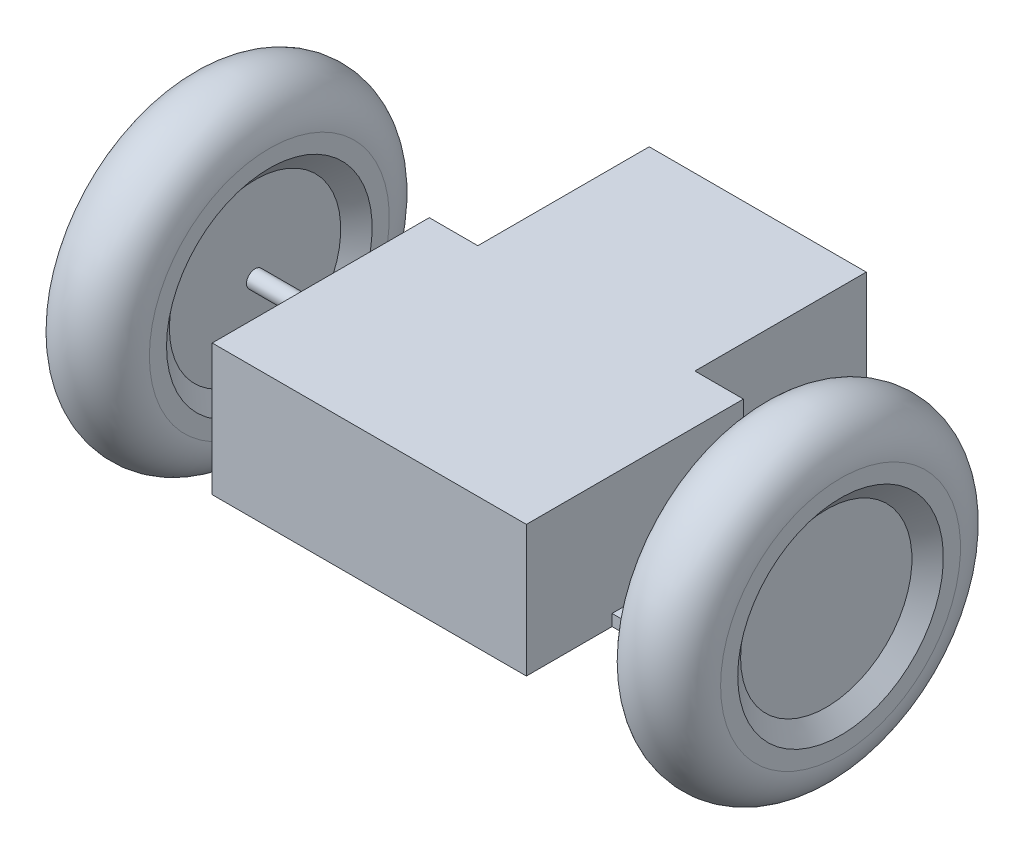
SolidWorks part; units mm, degrees
ref_plane "Front Plane" through (0, 0, 0) normal (0, 0, 1) x (1, 0, 0)
ref_plane "Top Plane" through (0, 0, 0) normal (0, 1, 0) x (1, 0, 0)
ref_plane "Right Plane" through (0, 0, 0) normal (1, 0, 0) x (0, 0, -1)
sketch "Sketch1" plane through (0, 0, 0) normal (0, 1, 0) x (1, 0, 0)
  line L1 (27.5, 34) -> (-27.5, 34)
  line L2 (27.5, 34) -> (27.5, -34)
  line L3 (27.5, -34) -> (-27.5, -34)
  line L4 (-27.5, 34) -> (-27.5, -34)
  line L5 (27.5, 34) -> (-27.5, -34) construction
  line L6 (27.5, -34) -> (-27.5, 34) construction
  point P0 (0, 0)
  dimension "D1" = 55
  dimension "D2" = 68
extrude "Boss-Extrude1" add sketch "Sketch1" along normal blind 11.5 and the other way blind 11.5
sketch "Sketch2" plane through (27.5, 0, 0) normal (1, 0, 0) x (0, 0, -1)
  line L0 (-40, 0) -> (49960, 0) construction
  line L1 (-34, 11.5) -> (-34, -11.5) construction
  circle A0 centre (-9, 0) radius 1.5
  point P4 (-34, 0)
  dimension "D2" = 3
  dimension "D1" = 25
extrude "Boss-Extrude2" add sketch "Sketch2" along normal blind 15
sketch "Sketch6" plane through (0, 0, 0) normal (0, 1, 0) x (1, 0, 0)
  line L0 (42.5, -7.5) -> (45, -7.5)
  line L1 (45, -7.5) -> (45, 6)
  line L2 (45, 6) -> (42.5, 9)
  line L3 (42.5, 9) -> (42.5, 12)
  line L4 (57.5, 12) -> (57.5, 9)
  line L5 (57.5, 9) -> (55, 6)
  line L6 (55, 6) -> (55, -9)
  line L7 (55, -9) -> (42.5, -9)
  line L8 (42.5, -9) -> (42.5, -7.5)
  line L9 (50, 0.5303) -> (50, -49999.4697) construction
  line L10 (42.5, 9) -> (50042.5, 9) construction
  line L11 (45, 6) -> (50045, 6) construction
  line L12 (42.5, -10.5) -> (42.5, -7.5) construction
  line L13 (42.5, -9) -> (50042.5, -9) construction
  arc A0 (42.5, 12) -> (57.5, 12) centre (50, 12) cw
  point P23 (42.5, -9)
  dimension "D1" = 21
  dimension "D2" = 7.5
  dimension "D3" = 10
  dimension "D4" = 3
  dimension "D5" = 3
revolve "Revolve1" add sketch "Sketch6" angle 360 about L13
mirror "Mirror1" about plane through (0, 0, 0) normal (1, 0, 0) of "Revolve1", "Boss-Extrude2"
sketch "Sketch7" plane through (0, 11.5, 0) normal (0, 1, 0) x (1, 0, 0)
  line L0 (0, 0) -> (0, 50000) construction
  line L1 (-27.5, 34) -> (-19, 34)
  line L2 (-27.5, 34) -> (-27.5, 4)
  line L3 (-27.5, 4) -> (-19, 4)
  line L4 (-19, 34) -> (-19, 4)
  line L5 (27.5, 34) -> (19, 34)
  line L6 (27.5, 34) -> (27.5, 4)
  line L7 (27.5, 4) -> (19, 4)
  line L8 (19, 34) -> (19, 4)
  dimension "D1" = 38
  dimension "D2" = 30
extrude "Cut-Extrude1" cut sketch "Sketch7" against normal through all
sketch "Sketch8" plane through (0, -11.5, 0) normal (0, -1, 0) x (1, 0, 0)
  line L0 (-27.5, -4) -> (-27.5, 34) construction
  line L1 (-27.5, 19) -> (-32.5, 19)
  line L2 (-27.5, 19) -> (-27.5, 11)
  line L3 (-27.5, 11) -> (-32.5, 11)
  line L4 (-32.5, 19) -> (-32.5, 11)
  line L5 (27.5, 34) -> (27.5, -4) construction
  line L6 (27.5, 19) -> (32.5, 19)
  line L7 (27.5, 19) -> (27.5, 11)
  line L8 (27.5, 11) -> (32.5, 11)
  line L9 (32.5, 19) -> (32.5, 11)
  line L10 (0, 0) -> (0, -50000) construction
  line L12 (27.5, 15) -> (-49972.5, 15) construction
  line L13 (-27.5, 34) -> (27.5, 34) construction
  circle A0 centre (30, 15) radius 1.5
  circle A1 centre (-30, 15) radius 1.5
  point P17 (27.5, 15)
  dimension "D5" = 3
  dimension "D1" = 5
  dimension "D2" = 8
  dimension "D3" = 19
  dimension "D4" = 60
extrude "Boss-Extrude3" add sketch "Sketch8" against normal blind 2
